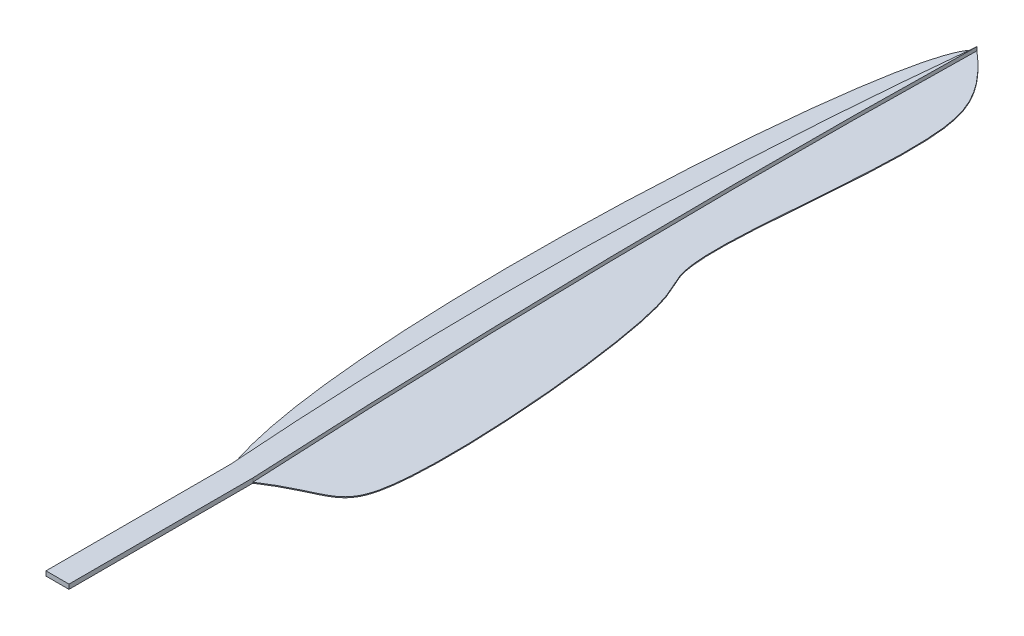
SolidWorks part; units mm, degrees
ref_plane "Front Plane" through (0, 0, 0) normal (0, 0, 1) x (1, 0, 0)
ref_plane "Top Plane" through (0, 0, 0) normal (0, 1, 0) x (1, 0, 0)
ref_plane "Right Plane" through (0, 0, 0) normal (1, 0, 0) x (0, 0, -1)
sketch "Sketch2" plane through (0, 0, 0) normal (0, 1, 0) x (1, 0, 0)
  line L0 (0, 0) -> (0, 160) construction
  line L1 (0, 0) -> (0, -40) construction
  line L3 (-2.5, 0) -> (2.5, 0) construction
  line L4 (-2.5, 0) -> (-2.5, -40)
  line L5 (-2.5, -40) -> (2.5, -40)
  line L6 (2.5, 0) -> (2.5, -40)
  spline S0 degree 3 poles (2.5, 0) (12.1714, 6.4678) (22.6995, 1.2616) (16.0202, 76.7765) (5.944, 89.5579) (14.6334, 135.7202) (8.5852, 152.5959) (0, 160) knots 0 0 0 0 0.195492 0.49428 0.56869 0.865179 1 1 1 1
  spline S1 degree 2 poles (2.5, 0) (-1.6392, 79.8302) (0, 160) knots 0 0 0 1 1 1
  spline S2 degree 2 poles (-2.5, 0) (-8.3315, 79.8852) (0, 160) knots 0 0 0 1 1 1
  spline S3 degree 3 poles (0, 160) (-8.9826, 157.0281) (-16.5, 35.9065) (-2.5, 0) knots 0 0 0 0 1 1 1 1
  dimension "D1" = 5
  dimension "40" = 40
  dimension "160" = 160
extrude "Boss-Extrude1" add sketch "Sketch2" along normal blind 1 contours S2 L4 L5 L6 S1 region at (-1.3487, 0, -42.7498)
extrude "Boss-Extrude2" add sketch "Sketch2<4>" along normal blind 0.2 contours S1 S0 | S2 S3 region at (-6.2102, 0, -82.3953) region at (7.3196, 0, -71.2426)
sketch "Sketch2<4>" plane through (0, 0, 0) normal (0, 1, 0) x (1, 0, 0) same geometry as "Sketch2"
